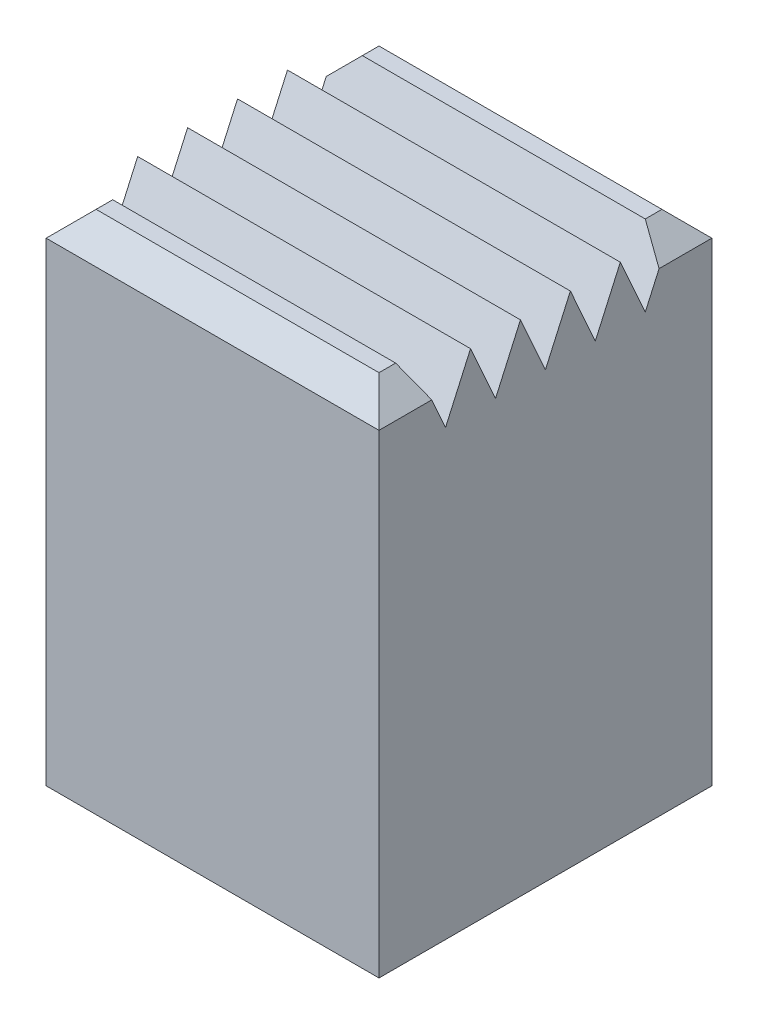
SolidWorks part; units mm, degrees
ref_plane "Front Plane" through (0, 0, 0) normal (0, 0, 1) x (1, 0, 0)
ref_plane "Top Plane" through (0, 0, 0) normal (0, 1, 0) x (1, 0, 0)
ref_plane "Right Plane" through (0, 0, 0) normal (1, 0, 0) x (0, 0, -1)
sketch "Sketch1" plane through (0, 0, 0) normal (0, 1, 0) x (1, 0, 0)
  line L1 (0, 0) -> (4, 0)
  line L2 (0, 0) -> (0, 4)
  line L3 (0, 4) -> (4, 4)
  line L4 (4, 0) -> (4, 4)
  dimension "D1" = 4
extrude "Boss-Extrude1" add sketch "Sketch1" along normal blind 6
sketch "Sketch2" plane through (0, 0, 0) normal (0, -1, 0) x (1, 0, 0)
  line L0 (2, -0.45) -> (2, 0) construction
  line L1 (0.45, -0.45) -> (3.55, -0.45)
  line L2 (0.45, -0.45) -> (0.45, -3.55)
  line L3 (0.45, -3.55) -> (3.55, -3.55)
  line L4 (3.55, -0.45) -> (3.55, -3.55)
  line L5 (0, 0) -> (4, 0) construction
  line L6 (0.45, -2) -> (0, -2) construction
  line L7 (0, -4) -> (0, 0) construction
  point P12 (0, 0)
  dimension "D1" = 3.1
extrude "Cut-Extrude1" cut sketch "Sketch2" against normal blind 4.9
sketch "Sketch3" plane through (0, 0, 0) normal (-1, 0, 0) x (0, 0, 1)
  line L0 (-3.5, 6) -> (-3.2, 5.33)
  line L1 (-4, 6) -> (0, 6) construction
  line L2 (-3.2, 5.33) -> (-2.9, 6)
  line L3 (-3.5, 6) -> (-2.9, 6)
  dimension "D1" = 0.5
  dimension "D2" = 0.6
  dimension "D3" = 0.67
extrude "Cut-Extrude2" cut sketch "Sketch3" against normal up to surface (4 mm away) contours L3 L2 L0 up to face at (4, 3, -2)
pattern_linear "LPattern1" count 5 spacing 0.6 along (0, 0, 1) of "Cut-Extrude2"
chamfer "Chamfer1" distance 0.3 angle 45 6 edges at (4, 6, -0.25) (2, 6, 0) (0, 6, -0.25) (0, 6, -3.75) (2, 6, -4) (4, 6, -3.75)
